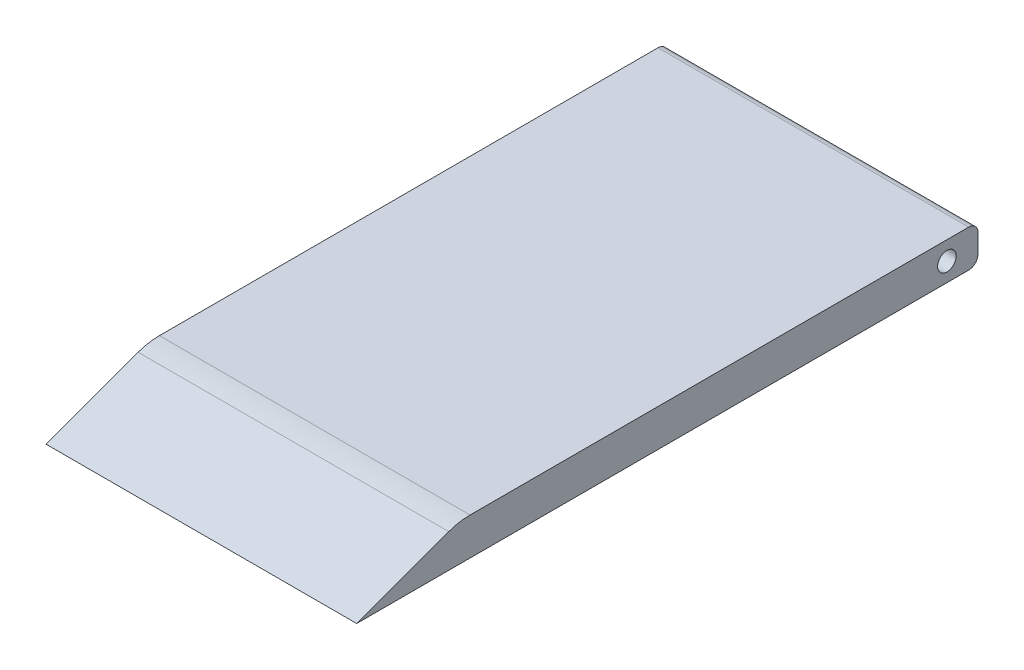
SolidWorks part; units mm, degrees
ref_plane "Front Plane" through (0, 0, 0) normal (0, 0, 1) x (1, 0, 0)
ref_plane "Top Plane" through (0, 0, 0) normal (0, 1, 0) x (1, 0, 0)
ref_plane "Right Plane" through (0, 0, 0) normal (1, 0, 0) x (0, 0, -1)
sketch "Sketch1" plane through (0, 0, 0) normal (0, 1, 0) x (1, 0, 0)
  line L0 (0, 0) -> (50, 0)
  line L1 (0, 0) -> (0, -100)
  line L2 (0, -100) -> (50, -100)
  line L3 (50, -100) -> (50, 0)
  dimension "D1" = 50
  dimension "D2" = 100
extrude "Boss-Extrude1" add sketch "Sketch1" along normal blind 6
sketch "Sketch2" plane through (50, 0, 0) normal (1, 0, 0) x (0, 0, -1)
  line L0 (-5, 13.7474) -> (-5, -12.8969) construction
  line L1 (0, 6) -> (0, 0) construction
  line L2 (0, 3) -> (-100, 3) construction
  line L3 (-100, 6) -> (-100, 0) construction
  circle A0 centre (-5, 3) radius 1.5
  dimension "D1" = 5
extrude "Cut-Extrude1" cut sketch "Sketch2" against normal through all
fillet "Fillet2" radius 1.5 2 edges at (25, 0, 0) (25, 6, 0)
chamfer "Chamfer1" distance 6 angle 70 1 edges at (25, 6, 100) first distance on face at (25, 3, 100)
fillet "Fillet3" radius 10 1 edges at (25, 6, 83.5151)
